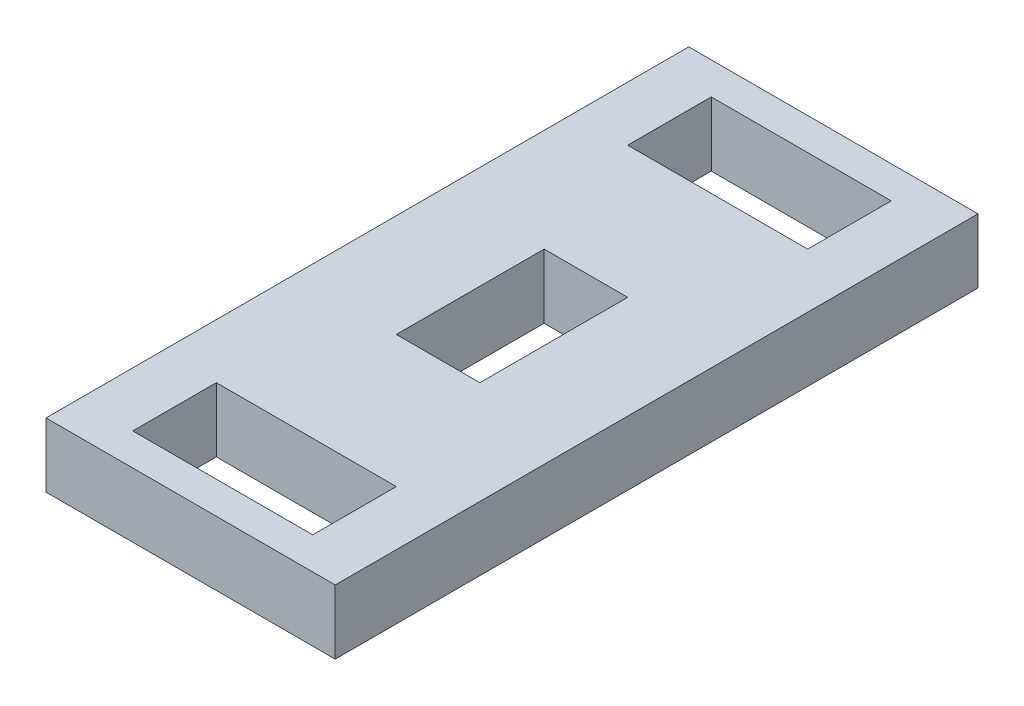
SolidWorks part; units mm, degrees
ref_plane "Plan de face" through (0, 0, 0) normal (0, 0, 1) x (1, 0, 0)
ref_plane "Plan de dessus" through (0, 0, 0) normal (0, 1, 0) x (1, 0, 0)
ref_plane "Plan de droite" through (0, 0, 0) normal (1, 0, 0) x (0, 0, -1)
sketch "Esquisse1" plane through (0, 0, 0) normal (0, 1, 0) x (1, 0, 0)
  line L0 (3.409, -1.8775) -> (3.409, -0.8775) construction
  line L1 (-1.091, 18.1225) -> (7.909, 18.1225)
  line L2 (-1.091, 18.1225) -> (-1.091, -1.8775)
  line L3 (-1.091, -1.8775) -> (7.909, -1.8775)
  line L4 (7.909, 18.1225) -> (7.909, -1.8775)
  line L5 (0.609, -0.8775) -> (6.209, -0.8775)
  line L6 (0.609, -0.8775) -> (0.609, 1.7225)
  line L7 (0.609, 1.7225) -> (6.209, 1.7225)
  line L8 (6.209, -0.8775) -> (6.209, 1.7225)
  line L9 (-1.091, 8.1225) -> (7.909, 8.1225) construction
  line L10 (0.609, 14.5225) -> (6.209, 14.5225)
  line L11 (6.209, 17.1225) -> (6.209, 14.5225)
  line L12 (0.609, 17.1225) -> (6.209, 17.1225)
  line L13 (0.609, 17.1225) -> (0.609, 14.5225)
  dimension "D1" = 20
  dimension "D2" = 9
  dimension "D3" = 1
  dimension "D4" = 5.6
  dimension "D5" = 2.6
extrude "Boss.-Extru.1" add sketch "Esquisse1" along normal blind 2 contours L4 L1 L2 L3 L13 L12 L11 L10 L8 L5 L6 L7 region at (3.409, 0, -8.1225)
sketch "Esquisse2" plane through (0, 0, 0) normal (0, -1, 0) x (1, 0, 0)
  line L0 (-1.091, -8.1225) -> (7.909, -8.1225) construction
  line L1 (-1.091, -18.1225) -> (-1.091, 1.8775) construction
  line L2 (7.909, -18.1225) -> (7.909, 1.8775) construction
  line L4 (4.709, -10.4225) -> (2.109, -10.4225)
  line L5 (4.709, -10.4225) -> (4.709, -5.8225)
  line L6 (4.709, -5.8225) -> (2.109, -5.8225)
  line L7 (2.109, -10.4225) -> (2.109, -5.8225)
  line L8 (4.709, -10.4225) -> (2.109, -5.8225) construction
  line L9 (4.709, -5.8225) -> (2.109, -10.4225) construction
  point P6 (3.409, -8.1225)
  point P11 (3.409, -8.1225)
  dimension "D1" = 4.6
  dimension "D2" = 2.6
extrude "Enlèv. mat.-Extru.1" cut sketch "Esquisse2" along normal through all and the other way through all contours L7 L4 L5 L6 region at (3.409, 0, -8.1225)
